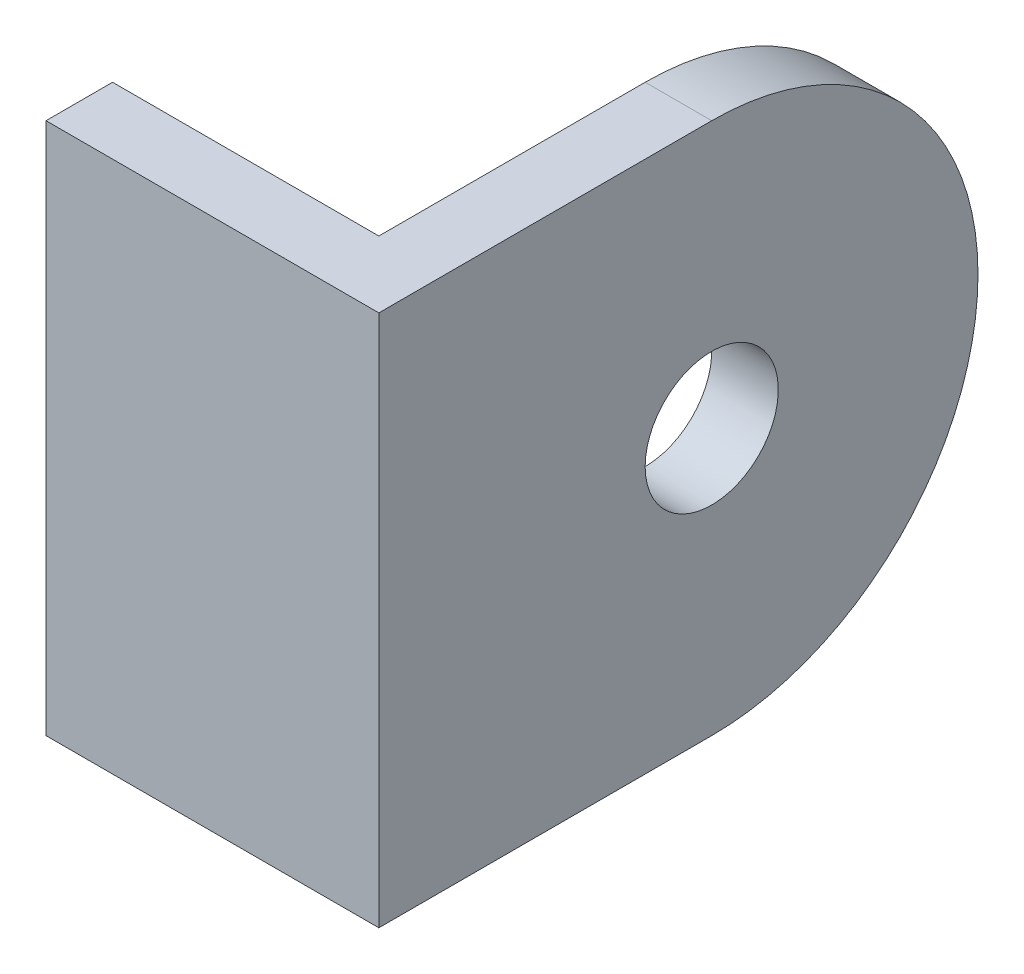
SolidWorks part; units mm, degrees
ref_plane "Front Plane" through (0, 0, 0) normal (0, 0, 1) x (1, 0, 0)
ref_plane "Top Plane" through (0, 0, 0) normal (0, 1, 0) x (1, 0, 0)
ref_plane "Right Plane" through (0, 0, 0) normal (1, 0, 0) x (0, 0, -1)
sketch "Sketch1" plane through (0, 0, 0) normal (0, 1, 0) x (1, 0, 0)
  line L4 (-4.4181, 15.2015) -> (0.5819, 15.2015)
  line L5 (0.5819, 15.2015) -> (0.5819, -29.7985)
  line L6 (0.5819, -29.7985) -> (-24.4181, -29.7985)
  line L7 (-24.4181, -29.7985) -> (-24.4181, -24.7985)
  line L8 (-24.4181, -24.7985) -> (-4.4181, -24.7985)
  line L9 (-4.4181, -24.7985) -> (-4.4181, 15.2015)
extrude "Boss-Extrude1" add sketch "Sketch1" along normal mid plane 40
sketch "Sketch2" plane through (-4.4181, 0, 0) normal (-1, 0, 0) x (0, 0, 1)
  circle A2 centre (4.7985, 0) radius 5
fillet "Fillet1" radius 20 1 edges at (-1.9181, -20, -15.2015)
fillet "Fillet2" radius 20 1 edges at (-1.9181, 20, -15.2015)
extrude "Cut-Extrude2" cut sketch "Sketch2" against normal blind 40
